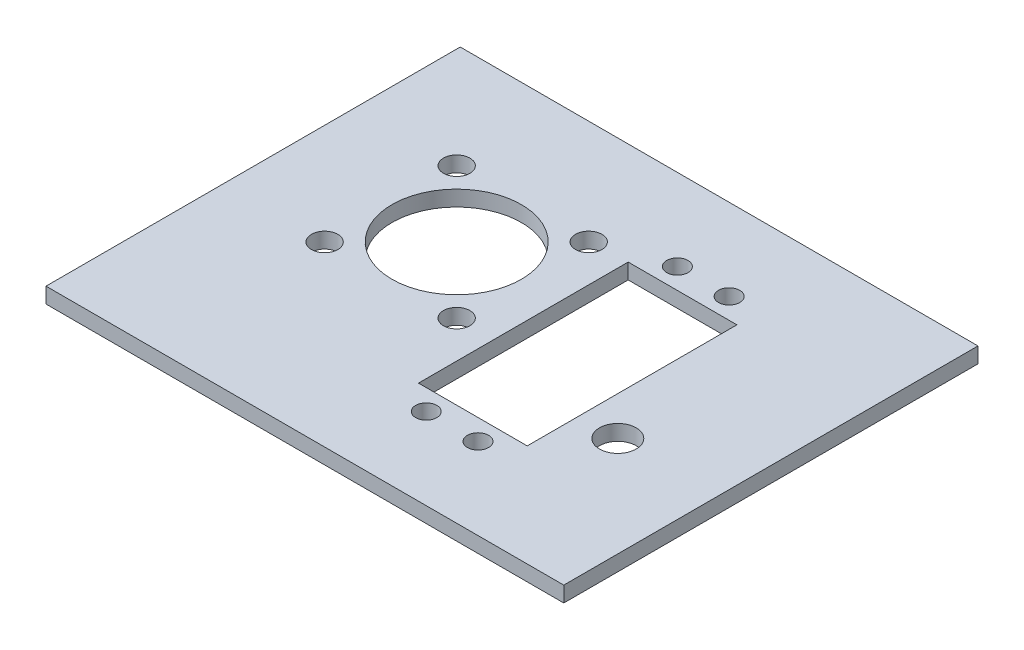
SolidWorks part; units mm, degrees
ref_plane "Płaszczyzna przednia" through (0, 0, 0) normal (0, 0, 1) x (1, 0, 0)
ref_plane "Płaszczyzna górna" through (0, 0, 0) normal (0, 1, 0) x (1, 0, 0)
ref_plane "Płaszczyzna prawa" through (0, 0, 0) normal (1, 0, 0) x (0, 0, -1)
sketch "Szkic1" plane through (0, 0, 0) normal (0, 1, 0) x (1, 0, 0)
  line L6 (-19.1495, 10.9626) -> (6.3505, -14.5374) construction
  line L11 (-38.6633, 31.161) -> (61.3367, 31.161)
  line L12 (-38.6633, 31.161) -> (-38.6633, -48.839)
  line L13 (-38.6633, -48.839) -> (61.3367, -48.839)
  line L14 (61.3367, 31.161) -> (61.3367, -48.839)
  line L15 (-19.1495, -14.5374) -> (6.3505, 10.9626) construction
  line L17 (13.5251, 11.411) -> (34.5251, 11.411)
  line L18 (13.5251, 11.411) -> (13.5251, -29.089)
  line L23 (13.5251, -29.089) -> (34.5251, -29.089)
  line L24 (34.5251, 11.411) -> (34.5251, -29.089)
  circle A0 centre (-6.3995, -1.7874) radius 12.5
  circle A2 centre (-19.1495, 10.9626) radius 2.55
  circle A3 centre (6.3505, 10.9626) radius 2.55
  circle A4 centre (6.3505, -14.5374) radius 2.55
  circle A5 centre (-19.1495, -14.5374) radius 2.55
  circle A6 centre (19.0251, 15.411) radius 2.05
  circle A7 centre (29.0251, 15.411) radius 2.05
  circle A8 centre (19.0251, -33.089) radius 2.05
  circle A9 centre (29.0251, -33.089) radius 2.05
  circle A10 centre (24.0251, -19.089) radius 0.5
  circle A11 centre (-6.3995, -1.7874) radius 0.5
  circle A12 centre (42.0251, -19.089) radius 3.55
  circle A13 centre (42.0251, -19.089) radius 0.5
  point P18 (24.0251, -29.089)
  point P22 (24.0251, 11.411)
  dimension "D3" = 10
  dimension "D5" = 4
  dimension "D13" = 35
  dimension "D18" = 19.75
  dimension "D20" = 5.1
  dimension "D22" = 25
  dimension "D23" = 7.1
  dimension "D24" = 4.1
  dimension "D1" = 100
  dimension "D2" = 80
  dimension "D4" = 10.5
  dimension "D6" = 4
  dimension "D7" = 5
  dimension "D8" = 5
  dimension "D9" = 4
  dimension "D10" = 4
  dimension "D11" = 5
  dimension "D12" = 5
  dimension "D14" = 18
  dimension "D15" = 40.5
  dimension "D16" = 21
  dimension "D17" = 10
  dimension "D19" = 19.75
  dimension "D21" = 25.5
extrude "Dodanie-wyciągnięcie1" add sketch "Szkic1" along normal blind 3 contours L14 L11 L12 L13 A12 A9 A8 A7 A6 A5 A4 A3 A2 A0 L17 L24 L23 L18 region at (10.9479, 0, 9.399)
